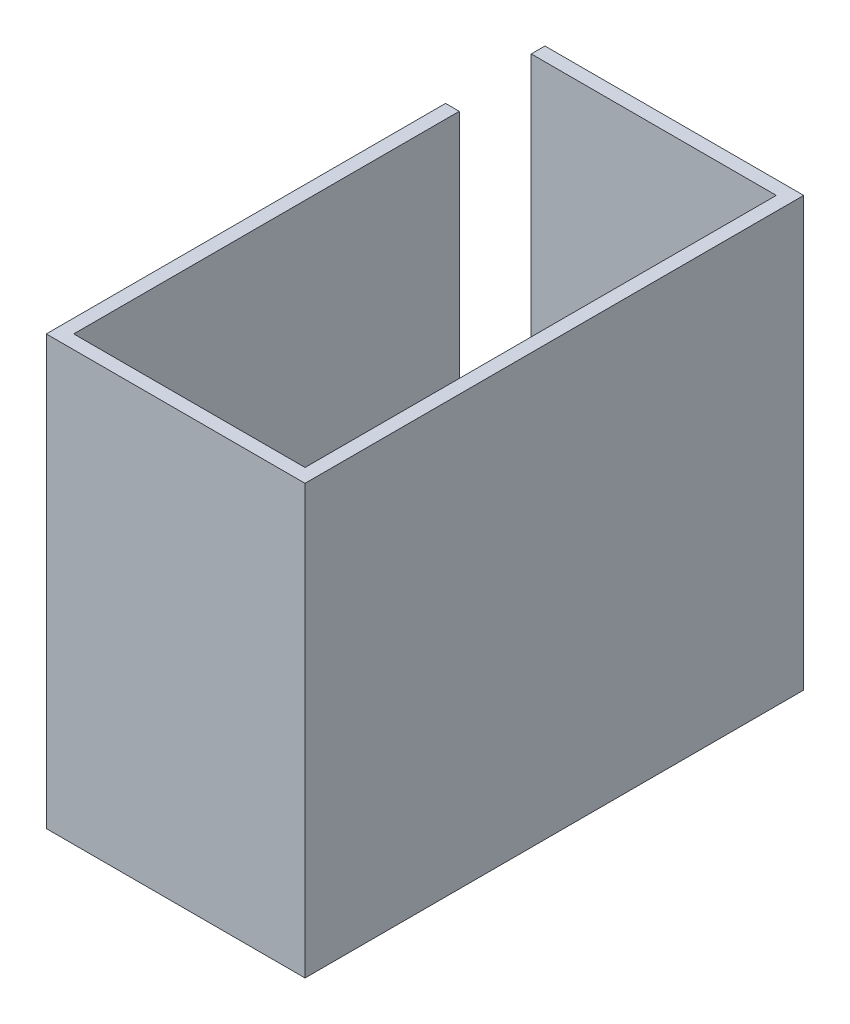
SolidWorks part; units mm, degrees
ref_plane "Front Plane" through (0, 0, 0) normal (0, 0, 1) x (1, 0, 0)
ref_plane "Top Plane" through (0, 0, 0) normal (0, 1, 0) x (1, 0, 0)
ref_plane "Right Plane" through (0, 0, 0) normal (1, 0, 0) x (0, 0, -1)
sketch "Sketch1" plane through (0, 0, 0) normal (0, 1, 0) x (1, 0, 0)
  line L1 (13.5, -22.5) -> (-13.5, -22.5)
  line L2 (13.5, -22.5) -> (13.5, 32.5)
  line L3 (13.5, 32.5) -> (-15.1, 32.5)
  line L4 (-13.5, -22.5) -> (-13.5, 22.5)
  line L5 (-13.5, 0) -> (13.5, 0) construction
  line L6 (0, 0) -> (0, -22.5) construction
  line L7 (15.1, -24.1) -> (-15.1, -24.1)
  line L8 (15.1, -24.1) -> (15.1, 34.1)
  line L9 (15.1, 34.1) -> (-15.1, 34.1)
  line L10 (-15.1, -24.1) -> (-15.1, 22.5)
  line L11 (-15.1, 22.5) -> (-13.5, 22.5)
  line L12 (-15.1, 22.5) -> (-15.1, 32.5)
  line L13 (-15.1, 34.1) -> (-15.1, 32.5)
  point P1 (-15.1036, 32.3899)
  point P5 (0, 0)
  point P11 (13.3, -24.1586)
  point P18 (13.3, -22.6366)
  dimension "D1" = 1.6
  dimension "D2" = 27
  dimension "D3" = 1.6
  dimension "D4" = 1.6
  dimension "D5" = 55
  dimension "D6" = 1.6
  dimension "D7" = 45
extrude "Boss-Extrude2" add sketch "Sketch1" along normal blind 50 contours L10 L7 L8 L9 L13 L3 L2 L1 L4 region at (14.1557, 0, -5)
extrude "Boss-Extrude3" add sketch "Sketch1<4>" along normal offset from surface (15 mm away) 35 contours L4 L1 L2 L3 L13 region at (-0.1524, 0, -5.2398) up to face at (-3.02, 50, -8.5)
sketch "Sketch1<4>" plane through (0, 0, 0) normal (0, 1, 0) x (1, 0, 0) same geometry as "Sketch1"
